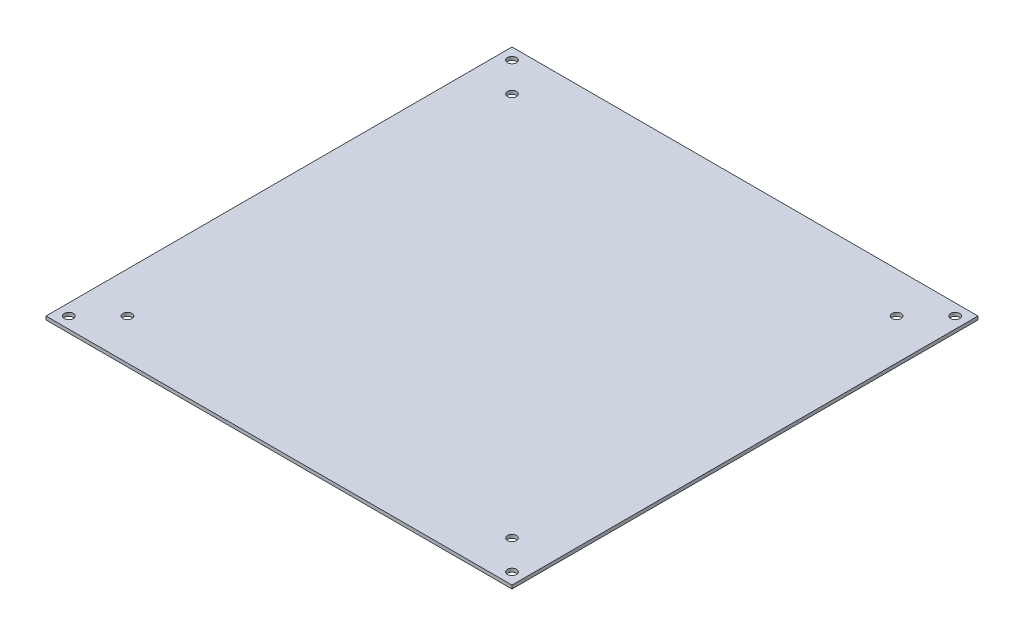
SolidWorks part; units mm, degrees
material "PC High Viscosity"
ref_plane "Front Plane" through (0, 0, 0) normal (0, 0, 1) x (1, 0, 0)
ref_plane "Top Plane" through (0, 0, 0) normal (0, 1, 0) x (1, 0, 0)
ref_plane "Right Plane" through (0, 0, 0) normal (1, 0, 0) x (0, 0, -1)
sketch "Sketch1" plane through (0, 0, 0) normal (0, 1, 0) x (1, 0, 0)
  line L0 (-101.8092, 0) -> (101.8092, 0) construction
  line L1 (-101.8092, 101.8092) -> (101.8092, 101.8092) construction
  line L2 (-101.8092, 101.8092) -> (-101.8092, -101.8092) construction
  line L3 (-101.8092, -101.8092) -> (101.8092, -101.8092) construction
  line L4 (101.8092, 101.8092) -> (101.8092, -101.8092) construction
  line L5 (-101.8092, 101.8092) -> (101.8092, -101.8092) construction
  line L6 (-101.8092, -101.8092) -> (101.8092, 101.8092) construction
  line L7 (-107.0543, 107.0543) -> (107.0543, 107.0543)
  line L8 (107.0543, 107.0543) -> (107.0543, -107.0543)
  line L9 (107.0543, -107.0543) -> (-107.0543, -107.0543)
  line L10 (-107.0543, -107.0543) -> (-107.0543, 107.0543)
  circle A0 centre (-101.8092, 101.8092) radius 2.0701
  circle A1 centre (-101.8092, -101.8092) radius 2.0701
  circle A2 centre (101.8092, -101.8092) radius 2.0701
  circle A3 centre (101.8092, 101.8092) radius 2.0701
  circle A4 centre (-88.3388, 88.3388) radius 2.0701
  circle A5 centre (88.3388, -88.3388) radius 2.0701
  circle A6 centre (88.3388, 88.3388) radius 2.0701
  circle A7 centre (-88.3388, -88.3388) radius 2.0701
  circle A8 centre (-101.8092, 101.8092) radius 5.2451 construction
  circle A9 centre (101.8092, 101.8092) radius 5.2451 construction
  circle A10 centre (101.8092, -101.8092) radius 5.2451 construction
  circle A11 centre (-101.8092, -101.8092) radius 5.2451 construction
  point P0 (0, 0)
  point P30 (0, 0)
  dimension "D2" = 4.1402
  dimension "D4" = 3.175
  dimension "D1" = 203.6183
  dimension "D3" = 19.05
  dimension "D5" = 4
extrude "Boss-Extrude1" add sketch "Sketch1" along normal blind 1.5875
